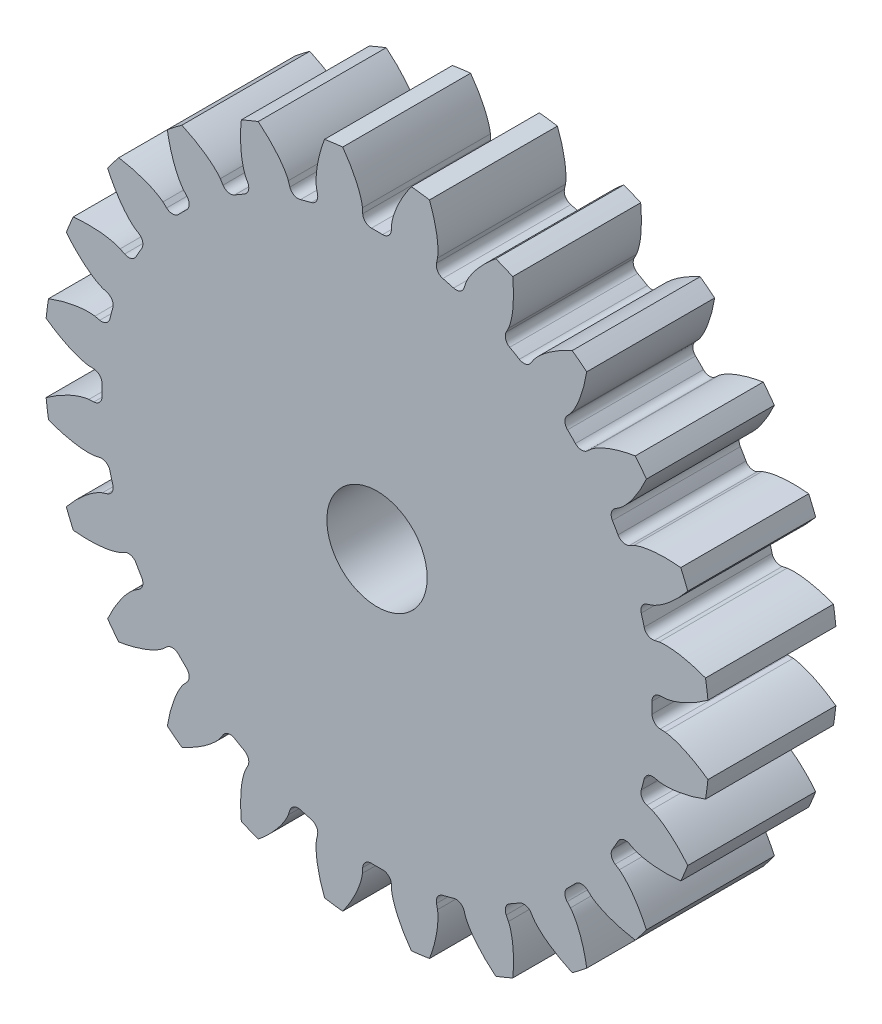
SolidWorks part; units mm, degrees
ref_plane "Front Plane" through (0, 0, 0) normal (0, 0, 1) x (1, 0, 0)
ref_plane "Top Plane" through (0, 0, 0) normal (0, 1, 0) x (1, 0, 0)
ref_plane "Right Plane" through (0, 0, 0) normal (1, 0, 0) x (0, 0, -1)
sketch "Sketch1" plane through (0, 0, 0) normal (0, 0, 1) x (1, 0, 0)
  line L0 (0, 0) -> (0, 15.24) construction
  line L1 (-4.898, 17.0227) -> (4.898, 13.4573) construction
  circle A0 centre (0, 0) radius 13.6525 construction
  circle A1 centre (0, 0) radius 16.51 construction
  circle A2 centre (0, 0) radius 15.24 construction
  circle A3 centre (0, 0) radius 14.3209 construction
  circle A4 centre (0, 0) radius 6.35 construction
  circle A5 centre (0, 0) radius 12.319 construction
  point P8 (254, 0)
  point P13 (304.8, 0)
  dimension "OD | Outside Diameter" = 33.02
  dimension "Root Diameter" = 27.305
  dimension "Gear Pitch Diameter" = 30.48
  dimension "Base Diameter" = 28.6418
  dimension "For Shaft Diameter" = 12.7
  dimension "Hub Diameter" = 24.638
  dimension "Pressure Angle" = 20
  dimension "Number of Teeth" = 609.6
  dimension "Gear Pitch | Diametral Pitch" = 508
sketch "Sketch2" plane through (0, 0, 0) normal (1, 0, 0) x (0, 0, -1)
  line L0 (-11.938, 0) -> (11.938, 0) construction
  line L1 (-11.938, 16.51) -> (11.938, 16.51) construction
  point P2 (0, 16.51)
  point P4 (-0.762, 0)
  point P6 (-0.762, 16.51)
  dimension "Overall Width" = 23.876
  dimension "Hub Width" = 11.176
  dimension "Face Width" = 12.7
sketch "Sketch3" plane through (0, 0, 0) normal (0, 0, 1) x (1, 0, 0)
  circle A0 centre (0, 0) radius 16.51
  circle A1 centre (0, 0) radius 16.51 construction
extrude "Boss-Extrude1" add sketch "Sketch3" against normal up to vertex (11.938 mm away) and the other way up to vertex (11.938 mm away) up to point (0, 0, -11.938) other way up to point (0, 0, 11.938)
sketch "Sketch5" plane through (0, 0, 0) normal (1, 0, 0) x (0, 0, -1)
  line L1 (-11.938, 16.51) -> (-0.762, 16.51)
  line L2 (-11.938, 16.51) -> (-11.938, 12.319)
  line L3 (-11.938, 12.319) -> (-0.762, 12.319)
  line L4 (-0.762, 16.51) -> (-0.762, 12.319)
  line L11 (11.938, 6.35) -> (-11.938, 6.35)
  line L12 (11.938, 6.35) -> (11.938, 0)
  line L13 (11.938, 0) -> (-11.938, 0)
  line L14 (-11.938, 6.35) -> (-11.938, 0)
  point P5 (0, 6.35)
  point P12 (0, 12.319)
revolve "Cut-Revolve1" cut sketch "Sketch5" angle 360 about L0
fillet "Fillet2" radius 0.4261 6 edges at (16.51, 0, -11.938) (6.35, 0, -11.938) (6.35, 0, 11.938) (12.319, 0, 0.762) (16.51, 0, 0.762) (12.319, 0, 11.938)
sketch "Sketch4" plane through (0, 0, 0) normal (0, 0, 1) x (1, 0, 0)
  line L0 (0, 0) -> (13.6351, 0.6898) construction
  line L2 (0, 0) -> (13.6351, -0.6898) construction
  line L4 (13.6351, 0.6898) -> (14.3026, 0.7235)
  line L5 (14.3026, -0.7235) -> (13.6351, -0.6898)
  arc A0 (13.6351, 0.6898) -> (13.6351, -0.6898) centre (0, 0) cw
  arc A3 (16.4219, 1.7037) -> (16.4219, -1.7037) centre (0, 0) cw
  circle A4 centre (0, 0) radius 16.51 construction
  spline S0 degree 4 poles (14.3026, 0.7235) (14.3061, 0.7238) (14.3158, 0.7245) (14.3342, 0.7264) (14.3642, 0.7303) (14.4023, 0.7363) (14.4514, 0.7453) (14.509, 0.7575) (14.5722, 0.7725) (14.6407, 0.7907) (14.7089, 0.8104) (14.7766, 0.8315) (14.8439, 0.8538) (14.9252, 0.8825) (15.0222, 0.919) (15.1351, 0.9648) (15.2624, 1.0204) (15.3912, 1.0811) (15.5174, 1.144) (15.644, 1.2113) (15.7659, 1.279) (15.8915, 1.3531) (16.0071, 1.4235) (16.1354, 1.5064) (16.2387, 1.5746) (16.3736, 1.6689) (16.453, 1.7259) (16.5454, 1.7941) (16.5862, 1.8252) (16.6114, 1.8444) knots 0 0 0 0 0 0.005377 0.015084 0.028532 0.04661 0.064855 0.092111 0.119476 0.146842 0.174209 0.201575 0.228941 0.256307 0.307035 0.361767 0.4165 0.471232 0.525964 0.580697 0.635429 0.690161 0.744894 0.799626 0.854358 0.909091 0.954545 1 1 1 1 1 construction
  spline S1 degree 4 poles (14.3026, 0.7235) (14.3061, 0.7238) (14.3158, 0.7245) (14.3342, 0.7264) (14.3642, 0.7303) (14.4023, 0.7363) (14.4514, 0.7453) (14.509, 0.7575) (14.5722, 0.7725) (14.6407, 0.7907) (14.7089, 0.8104) (14.7766, 0.8315) (14.8439, 0.8538) (14.9252, 0.8825) (15.0222, 0.919) (15.1351, 0.9648) (15.2624, 1.0204) (15.3912, 1.0811) (15.5174, 1.144) (15.644, 1.2113) (15.7659, 1.279) (15.8915, 1.3531) (16.0071, 1.4235) (16.1354, 1.5064) (16.2387, 1.5746) (16.3444, 1.6484) (16.3957, 1.6849) (16.4219, 1.7037) knots 0 0 0 0 0 0.005377 0.015084 0.028532 0.04661 0.064855 0.092111 0.119476 0.146842 0.174209 0.201575 0.228941 0.256307 0.307035 0.361767 0.4165 0.471232 0.525964 0.580697 0.635429 0.690161 0.744894 0.799626 0.854358 0.909091 0.909091 0.909091 0.909091 0.909091
  spline S2 degree 4 poles (14.3026, -0.7235) (14.3061, -0.7238) (14.3158, -0.7245) (14.3342, -0.7264) (14.3642, -0.7303) (14.4023, -0.7363) (14.4514, -0.7453) (14.509, -0.7575) (14.5722, -0.7725) (14.6407, -0.7907) (14.7089, -0.8104) (14.7766, -0.8315) (14.8439, -0.8538) (14.9252, -0.8825) (15.0222, -0.919) (15.1351, -0.9648) (15.2624, -1.0204) (15.3912, -1.0811) (15.5174, -1.144) (15.644, -1.2113) (15.7659, -1.279) (15.8915, -1.3531) (16.0071, -1.4235) (16.1354, -1.5064) (16.2387, -1.5746) (16.3736, -1.6689) (16.453, -1.7259) (16.5454, -1.7941) (16.5862, -1.8252) (16.6114, -1.8444) knots 0 0 0 0 0 0.005377 0.015084 0.028532 0.04661 0.064855 0.092111 0.119476 0.146842 0.174209 0.201575 0.228941 0.256307 0.307035 0.361767 0.4165 0.471232 0.525964 0.580697 0.635429 0.690161 0.744894 0.799626 0.854358 0.909091 0.954545 1 1 1 1 1 construction
  spline S3 degree 4 poles (14.3026, -0.7235) (14.3061, -0.7238) (14.3158, -0.7245) (14.3342, -0.7264) (14.3642, -0.7303) (14.4023, -0.7363) (14.4514, -0.7453) (14.509, -0.7575) (14.5722, -0.7725) (14.6407, -0.7907) (14.7089, -0.8104) (14.7766, -0.8315) (14.8439, -0.8538) (14.9252, -0.8825) (15.0222, -0.919) (15.1351, -0.9648) (15.2624, -1.0204) (15.3912, -1.0811) (15.5174, -1.144) (15.644, -1.2113) (15.7659, -1.279) (15.8915, -1.3531) (16.0071, -1.4235) (16.1354, -1.5064) (16.2387, -1.5746) (16.3444, -1.6484) (16.3957, -1.6849) (16.4219, -1.7037) knots 0 0 0 0 0 0.005377 0.015084 0.028532 0.04661 0.064855 0.092111 0.119476 0.146842 0.174209 0.201575 0.228941 0.256307 0.307035 0.361767 0.4165 0.471232 0.525964 0.580697 0.635429 0.690161 0.744894 0.799626 0.854358 0.909091 0.909091 0.909091 0.909091 0.909091
  dimension "D1" = 27.305
extrude "Cut-Extrude1" cut sketch "Sketch4" against normal through all both and the other way through all
fillet "Fillet1" radius 0.4261 2 edges at (13.6351, -0.6898, -5.588) (13.6351, 0.6898, -5.588)
pattern_circular "CirPattern1" count 24 over 360 about axis through (0, 0, 11.938) along (0, 0, -1) of "Cut-Extrude1", "Fillet1"
sketch "Sketch6" plane through (0, 0, 0) normal (0, 0, 1) x (1, 0, 0)
  circle A0 centre (0, 0) radius 43.6094
extrude "Cut-Extrude2" cut sketch "Sketch6" along normal through all
extrude "Cut-Extrude3" cut sketch "Sketch6<2>" against normal through all from offset 6.35 offset against normal yes
sketch "Sketch6<2>" plane through (0, 0, 0) normal (0, 0, 1) x (1, 0, 0) same geometry as "Sketch6"
sketch "Sketch7" plane through (0, 0, 0) normal (0, 0, 1) x (1, 0, 0)
  circle A0 centre (0, 0) radius 6.35
  circle A1 centre (0, 0) radius 2.4892
  circle A2 centre (0, 0) radius 6.35 construction
  dimension "D1" = 4.9784
extrude "Boss-Extrude2" add sketch "Sketch7" against normal up to surface (6.35 mm away) up to face at (6.35, 0, -6.35)
equation "\"Root Diameter@Sketch1\"=\"Root Diameter\""
equation "\"OD | Outside Diameter@Sketch1\"=\"Outside Diameter\""
equation "\"D1@CirPattern1\"=\"Number of Teeth\""
equation "\"Diametral Pitch\"=20"
equation "\"Number of Teeth\"=24"
equation "\"Pressure Angle\"=20"
equation "\"Pitch Diameter\"= \"Number of Teeth\" / \"Diametral Pitch\""
equation "\"Base Diameter\"= \"Pitch Diameter\" * cos ( \"Pressure Angle\" )"
equation "\"Outside Diameter\"= ( \"Number of Teeth\" + 2 ) / \"Diametral Pitch\""
equation "\"Dedendum\"= 1.25 / \"Diametral Pitch\""
equation "\"Root Diameter\"= \"Pitch Diameter\" - ( 2 * \"Dedendum\" )"
equation "\"Pitch Angle\"= 360deg / \"Number of Teeth\""
equation "\"Alpha\"= sqr ( \"Pitch Diameter\" ^ 2 - \"Base Diameter\" ^ 2 ) / \"Base Diameter\" * 180 / PI - \"Pressure Angle\""
equation "\"Beta\"= ( \"Pitch Angle\" / 4 - \"Alpha\" )"
equation "\"Phi\"= sqr ( ( \"Outside Diameter\" / 2 ) ^ 2 - ( \"Base Diameter\" / 2 ) ^ 2 ) / ( \"Base Diameter\" / 2 )"
equation "\"Addendum\"= 1 / \"Diametral Pitch\""
equation "\"WorkingDepth\"= 2 / \"Diametral Pitch\""
equation "\"WholeDepth\"= 2.25 / \"Diametral Pitch\""
equation "\"Clearance\"= 0.25 / \"Diametral Pitch\""
equation "\"ToothThickness\"= ( pi * 2 ) / \"Diametral Pitch\""
equation "\"CircularPitch\"= pi / \"Diametral Pitch\""
equation "\"Number of Teeth@Sketch1\"=\"Number of Teeth\""
equation "\"Gear Pitch | Diametral Pitch@Sketch1\"=\"Diametral Pitch\""
equation "\"Pressure Angle@Sketch1\"=\"Pressure Angle\""
equation "\"Gear Pitch Diameter@Sketch1\"=\"Pitch Diameter\""
equation "\"Base Diameter@Sketch1\"=\"Base Diameter\""
equation "\"Fillet\"= \"Clearance\" * cos ( \"Pressure Angle\" ) * tan ( ( 90 + \"Pressure Angle\" ) / 2 )"
equation "\"D1@Fillet1\"=\"Fillet\""
equation "\"D1@Sketch4\"=if( \"Base Diameter\">\"Root Diameter\",\"Root Diameter\",\"Base Diameter\"-.00001)"
equation "\"D1@Fillet2\"=\"Fillet\""
